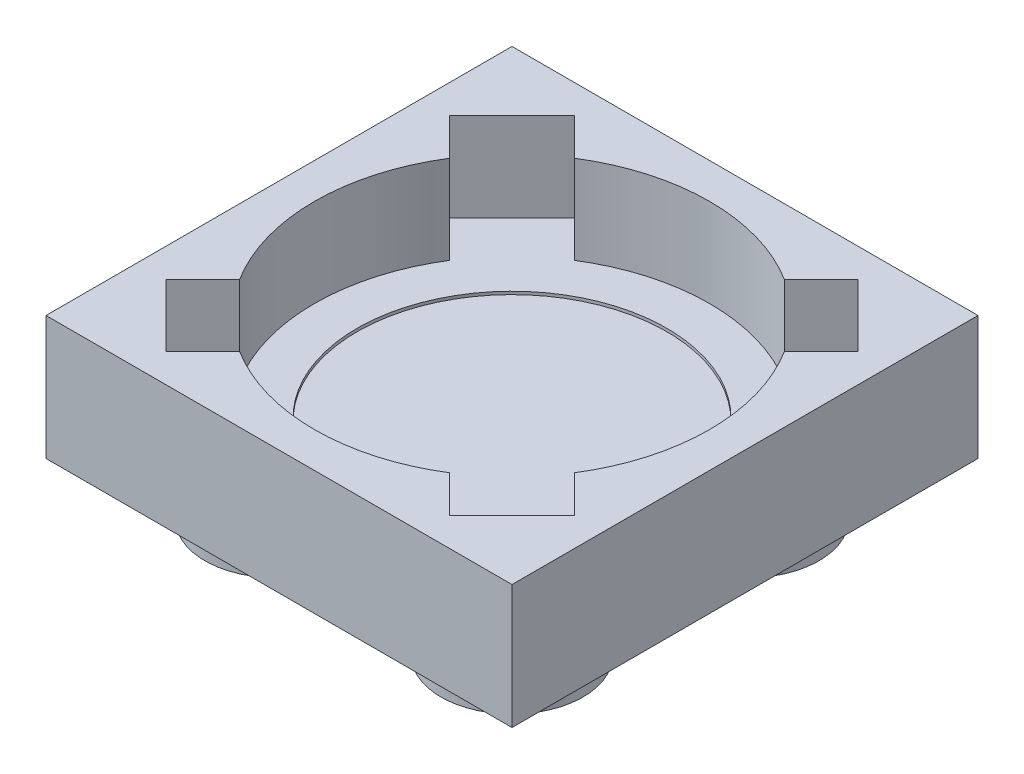
SolidWorks part; units mm, degrees
ref_plane "Front Plane" through (0, 0, 0) normal (0, 0, 1) x (1, 0, 0)
ref_plane "Top Plane" through (0, 0, 0) normal (0, 1, 0) x (1, 0, 0)
ref_plane "Right Plane" through (0, 0, 0) normal (1, 0, 0) x (0, 0, -1)
sketch "Sketch2" plane through (0, 0, 0) normal (0, 1, 0) x (1, 0, 0)
  line L1 (0, 0) -> (15.8, 0)
  line L2 (0, 0) -> (0, 15.8)
  line L3 (0, 15.8) -> (15.8, 15.8)
  line L4 (15.8, 0) -> (15.8, 15.8)
  dimension "D1" = 15.8
  dimension "D2" = 15.8
extrude "Boss-Extrude2" add sketch "Sketch2" against normal blind 4.2
sketch "Sketch4" plane through (0, 0, 0) normal (0, 1, 0) x (1, 0, 0)
  line L0 (15.8, 0) -> (15.8, 15.8) construction
  line L1 (14.6, 14.6) -> (1.2, 14.6)
  line L2 (14.6, 14.6) -> (14.6, 1.2)
  line L3 (14.6, 1.2) -> (1.2, 1.2)
  line L4 (1.2, 14.6) -> (1.2, 1.2)
  line L5 (0, -55) -> (0, 55) construction
  line L6 (-55, 0) -> (55, 0) construction
  line L7 (15.8, 15.8) -> (0, 15.8) construction
  dimension "D1" = 1.2
  dimension "D2" = 1.2
  dimension "D3" = 1.2
  dimension "D4" = 1.2
extrude "Cut-Extrude1" cut sketch "Sketch4" against normal offset from surface (3 mm away) 1.2 up to face at (7.9, -4.2, -7.9)
sketch "Sketch6" plane through (0, -4.2, 0) normal (0, -1, 0) x (-1, 0, 0)
  line L0 (-15.8, 0) -> (-15.8, 15.8) construction
  line L1 (-15.8, 15.8) -> (0, 15.8) construction
  circle A0 centre (-11.9, 11.9) radius 2.41
  dimension "D1" = 4.82
  dimension "D2" = 3.9
  dimension "D3" = 3.9
extrude "Boss-Extrude4" add sketch "Sketch6" along normal blind 1.8
pattern_linear "LPattern1" count 2 spacing 8 along (0, 0, 1) count 2 spacing 8 along (-1, 0, 0) of "Boss-Extrude4"
sketch "Sketch8" plane through (0, -3, 0) normal (0, 1, 0) x (1, 0, 0)
  line L0 (0, -3.3) -> (0, 3.3) construction
  line L1 (-3.3, 0) -> (3.3, 0) construction
  circle A0 centre (7.9, 7.9) radius 5.25
  point P27 (7.9, 7.9)
  dimension "D1" = 10.5
  dimension "D2" = 7.9
  dimension "D3" = 7.9
extrude "Cut-Extrude2" cut sketch "Sketch8" against normal blind 0.1
sketch "Sketch11" plane through (0, -3, 0) normal (0, 1, 0) x (1, 0, 0)
  line L1 (1.2, 14.6) -> (14.6, 14.6)
  line L2 (1.2, 14.6) -> (1.2, 1.2)
  line L3 (1.2, 1.2) -> (14.6, 1.2)
  line L4 (14.6, 14.6) -> (14.6, 1.2)
  circle A0 centre (7.9, 7.9) radius 6.7
  line M3 (14.6, 1.2) -> (14.6, 14.6)
  line M4 (14.6, 14.6) -> (1.2, 14.6)
  line M5 (1.2, 14.6) -> (1.2, 1.2)
  line M6 (1.2, 1.2) -> (14.6, 1.2)
extrude "Boss-Extrude9" add sketch "Sketch11" along normal up to surface (3 mm away) contours A0 L1 M5 | A0 L4 M4 | A0 L2 M6 | A0 L3 M3 region at (2.6966, -3, -13.1034) region at (13.1034, -3, -13.1034) region at (2.6966, -3, -2.6966) region at (13.1034, -3, -2.6966) up to face at (7.9, 0, -7.9)
sketch "Sketch12" plane through (0, 0, 0) normal (0, 1, 0) x (1, 0, 0)
  line L0 (0, 15.8) -> (3.1624, 12.6376)
  line L1 (0, -3.3) -> (0, 3.3) construction
  line L2 (15.8, 15.8) -> (0, 15.8) construction
  line L3 (2.1017, 11.577) -> (4.223, 13.6983)
  line L4 (2.1017, 11.577) -> (4.223, 13.6983)
  line L5 (2.1017, 11.577) -> (0.9704, 12.7083)
  line L6 (4.223, 13.6983) -> (3.0917, 14.8296)
  line L7 (0.9704, 12.7083) -> (3.0917, 14.8296)
  line L8 (2.1017, 11.577) -> (4.223, 13.6983)
  line L9 (2.1017, 11.577) -> (2.4236, 11.2551)
  line L10 (4.223, 13.6983) -> (4.5449, 13.3764)
  line L11 (2.4236, 11.2551) -> (4.5449, 13.3764)
  circle A0 centre (7.9, 7.9) radius 6.7 construction
  point P11 (3.1624, 12.6376)
  circle M2 centre (7.9, 7.9) radius 6.7
  dimension "D1" = 1.6
  dimension "D2" = 1.5
extrude "Cut-Extrude3" cut sketch "Sketch12" against normal offset from surface (3 mm away) 1.2 contours L7 L5 L3 L0 | L3 L9 M2 | L10 L3 M2 | L7 L0 L3 L6 | L9 L11 L10 M2 region at (3.127, 0, -13.7336) region at (2.0664, 0, -12.673) region at (2.4022, 0, -11.8054) region at (3.9946, 0, -13.3978) region at (3.341, 0, -12.459) up to face at (11.9, -4.2, -6.31)
ref_axis "Axis2" through (7.9, 0, -7.9) along (0, -1, 0)
pattern_circular "CirPattern3" count 4 every 90 about axis through (7.9, 0, -7.9) along (0, -1, 0) of "Cut-Extrude3"
sketch "Sketch18" plane through (-5.869, 0, -5.869) normal (0.7071, 0, 0.7071) x (0.7071, 0, -0.7071)
  line L0 (11.1723, 0) -> (11.1723, -3)
  line L1 (9.6723, 0) -> (12.6723, 0) construction
  line L2 (9.6723, -3) -> (12.6723, -3) construction
ref_plane "Plane2" through (7.9, 0, -7.9) normal (-0.7071, 0, 0.7071) x (0.7071, 0, 0.7071)
sketch "Sketch19" plane through (7.9, 0, -7.9) normal (-0.7071, 0, 0.7071) x (0.7071, 0, 0.7071)
  line L1 (-8.3, -3) -> (-6.2155, -3)
  line L2 (-8.3, -3) -> (-8.3, -2.1)
  line L3 (-8.3, -2.1) -> (-6.2155, -2.1)
  line L4 (-6.2155, -3) -> (-6.2155, -2.1)
  dimension "D1" = 0.9
